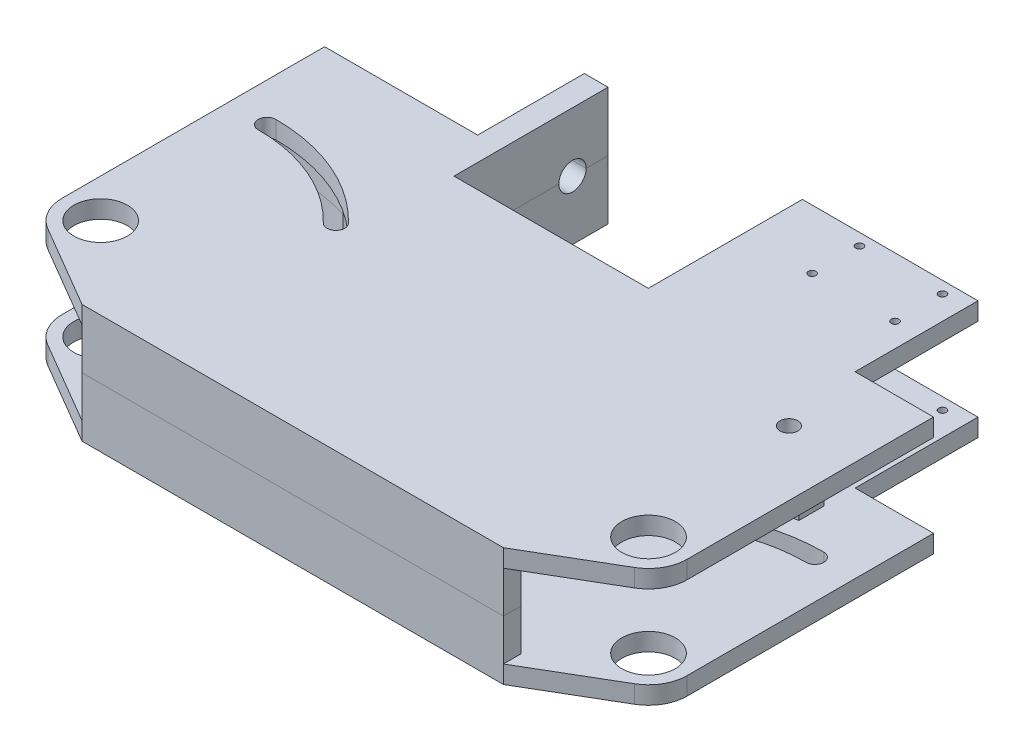
SolidWorks part; units mm, degrees
material "ABS"
ref_plane "Front Plane" through (0, 0, 0) normal (0, 0, 1) x (1, 0, 0)
ref_plane "Top Plane" through (0, 0, 0) normal (0, 1, 0) x (1, 0, 0)
ref_plane "Right Plane" through (0, 0, 0) normal (1, 0, 0) x (0, 0, -1)
sketch "Sketch1" plane through (0, 0, 0) normal (0, 1, 0) x (1, 0, 0)
  line L0 (0, 0) -> (0, 70.6916) construction
  line L1 (-112.9008, 0) -> (112.9008, 0)
  line L2 (166.7207, 38.2351) -> (89.7717, -234.2263) construction
  line L3 (126.8773, 49.4878) -> (49.9283, -222.9737) construction
  line L4 (146.799, 43.8615) -> (64.2237, -248.5217) construction
  line L5 (493.7687, -279.4) -> (979.2976, -279.4) construction
  line L6 (146.799, 43.8615) -> (146.799, 133.0155) construction
  line L7 (146.799, 133.0155) -> (-132.888, 133.0155) construction
  line L8 (19.05, -226.7236) -> (19.05, -291.7876) construction
  line L9 (-21.414, -217.1721) -> (256.1021, -295.5486) construction
  line L11 (146.799, 64.5625) -> (-146.799, 64.5625) construction
  line L12 (-146.799, 23.1605) -> (146.799, 23.1605) construction
  line L30 (-157.2662, 26.0018) -> (-112.9008, 0)
  line L31 (112.9008, 0) -> (157.2662, 26.0018)
  line L33 (-146.799, 43.8615) -> (-146.799, 133.0155) construction
  line L34 (-146.799, 133.0155) -> (132.888, 133.0155) construction
  line L38 (-167.5, 109.8697) -> (167.5, 109.8697) construction
  line L39 (-167.5, 43.8615) -> (-167.5, 184.5775)
  line L40 (-85.458, 241.7275) -> (-72.758, 241.7275)
  line L41 (-72.758, 241.7275) -> (-72.758, 159.1775)
  line L47 (125.4814, 175.878) -> (167.5, 175.878)
  line L51 (31.382, 159.1775) -> (31.382, 241.7275)
  line L52 (167.5, 43.8615) -> (167.5, 175.878)
  line L53 (31.382, 241.7275) -> (125.4814, 241.7275)
  line L54 (125.4814, 241.7275) -> (125.4814, 175.878)
  line L55 (68.3314, 209.9775) -> (112.7814, 235.3775) construction
  line L60 (112.7814, 235.3775) -> (68.3314, 235.3775) construction
  line L61 (112.7814, 235.3775) -> (112.7814, 209.9775) construction
  line L62 (112.7814, 209.9775) -> (68.3314, 209.9775) construction
  line L63 (68.3314, 235.3775) -> (68.3314, 209.9775) construction
  line L64 (112.7814, 209.9775) -> (68.3314, 235.3775) construction
  line L65 (-132.888, 184.5775) -> (-132.888, 81.4535) construction
  line L66 (-82.5723, 105.6948) -> (-146.799, 43.8615) construction
  line L67 (-85.458, 241.7275) -> (-85.458, 184.5775)
  line L68 (-85.458, 184.5775) -> (-167.5, 184.5775)
  line L69 (-72.758, 159.1775) -> (31.382, 159.1775)
  circle A0 centre (146.799, 43.8615) radius 14.351
  circle A2 centre (146.799, 43.8615) radius 20.701 construction
  circle A3 centre (69.85, -228.6) radius 14.351 construction
  circle A4 centre (69.85, -228.6) radius 20.701 construction
  circle A5 centre (69.85, -228.6) radius 50.8 construction
  circle A6 centre (99.1898, -124.7136) radius 50.8 construction
  circle A7 centre (-132.888, 133.0155) radius 4.7625
  circle A8 centre (-146.799, 43.8615) radius 14.351
  arc A9 (-157.2662, 26.0018) -> (-167.5, 43.8615) centre (-146.799, 43.8615) cw
  circle A10 centre (-132.888, 133.0155) radius 11.1125 construction
  circle A11 centre (146.799, 133.0155) radius 5.5563 construction
  circle A12 centre (-146.799, 43.8615) radius 20.701 construction
  arc A13 (-167.5, 43.8615) -> (-157.2662, 26.0018) centre (-146.799, 43.8615) cw construction
  circle A19 centre (132.888, 133.0155) radius 4.7625
  arc A20 (-146.799, 133.0155) -> (-82.5723, 105.6948) centre (-146.799, 43.8615) cw construction
  circle A28 centre (132.888, 133.0155) radius 11.1125 construction
  arc A35 (157.2662, 26.0018) -> (167.5, 43.8615) centre (146.799, 43.8615) ccw
  circle A39 centre (112.7814, 235.3775) radius 2.0193
  circle A40 centre (112.7814, 209.9775) radius 2.0193
  circle A41 centre (68.3314, 209.9775) radius 2.0193
  circle A42 centre (68.3314, 235.3775) radius 2.0193
  point P2 (85.3828, -173.6013)
  point P11 (0, 0)
  point P19 (19.05, -228.6)
  point P27 (83.6569, -179.7123)
  point P68 (-132.888, 133.0155)
  point P70 (90.5564, 222.6775)
  point P72 (0, 109.8697)
  point P78 (167.5, 109.8697)
  dimension "D2" = 28.702
  dimension "D6" = 101.6
  dimension "D12" = 9.525
  dimension "D16" = 11.1125
  dimension "D19" = 104.14
  dimension "D23" = 4.0386
  dimension "D5" = 89.154
  dimension "D7" = 6.35
  dimension "D8" = 279.4
  dimension "D9" = 279.687
  dimension "D10" = 296.926
  dimension "D11" = 19.05
  dimension "D13" = 146.799
  dimension "D17" = 6.35
  dimension "D18" = 94.742
  dimension "D20" = 82.55
  dimension "D21" = 57.15
  dimension "D25" = 6.35
  dimension "D22" = 25.4
  dimension "D24" = 44.45
  dimension "D26" = 12.7
  dimension "D27" = 36.9494
  dimension "D28" = 335
  dimension "D29" = 46.088
  dimension "D30" = 12.7
  dimension "D31" = 51.562
  dimension "D32" = 8.6995
  dimension "D3" = 6.35
  dimension "D4" = 6.35
  dimension "D14" = 6.35
  dimension "D15" = 6.35
extrude "Boss-Extrude1" add sketch "Sketch1" along normal mid plane 9.525 contours A0 A7 A8 region at (5.8545, 0, -103.4895)
sketch "Sketch6" plane through (0, 4.7625, 0) normal (0, 1, 0) x (1, 0, 0)
  line L11 (-112.9008, 9.525) -> (112.9008, 9.525)
  line L12 (-72.758, 159.1775) -> (125.4814, 159.1775)
  line L15 (-72.758, 241.7275) -> (-72.758, 159.1775) construction
  line L16 (-85.458, 241.7275) -> (-72.758, 241.7275) construction
  line L17 (-85.458, 241.7275) -> (-85.458, 184.5775) construction
  line L21 (-167.5, 43.8615) -> (-167.5, 184.5775) construction
  line L35 (-112.9008, 0) -> (112.9008, 0)
  line L38 (45.6521, 202.1035) -> (67.2858, 150.1296) construction
  line L39 (67.2858, 150.1296) -> (-83.7159, 144.9535) construction
  line L42 (115.9564, 136.6682) -> (115.9563, 202.1035) construction
  line L43 (115.9563, 202.1035) -> (45.6521, 202.1035) construction
  line L47 (31.3702, 211.6285) -> (53.2025, 159.1775) construction
  line L48 (125.4814, 145.7962) -> (125.4813, 211.6285) construction
  line L49 (125.4813, 211.6285) -> (31.3702, 211.6285) construction
  line L50 (125.4814, 241.7275) -> (125.4814, 175.878) construction
  line L51 (125.4814, 159.1775) -> (125.4814, 145.7962)
  line L53 (116.5914, 143.5241) -> (-116.5914, 143.5241)
  line L55 (-154.5631, 33.9416) -> (-112.9008, 9.525) construction
  line L56 (-83.7041, 194.8963) -> (-159.2482, 41.937) construction
  line L58 (112.9008, 9.525) -> (158.0561, 35.8748) construction
  line L59 (160.5644, 42.8499) -> (160.96, 134.7521) construction
  line L61 (160.96, 134.7521) -> (115.9564, 136.6682) construction
  line L63 (112.9008, 0) -> (112.9008, 9.525)
  line L64 (-83.7159, 144.9535) -> (-83.7041, 194.8963) construction
  line L65 (-83.7041, 194.8963) -> (-83.7041, 194.8963) construction
  line L66 (146.799, 43.8615) -> (146.799, 133.0155) construction
  line L67 (-85.458, 184.5775) -> (-167.5, 184.5775) construction
  line L68 (146.799, 43.8615) -> (146.799, 133.0155) construction
  line L69 (-146.799, 43.8615) -> (-146.799, 133.0155) construction
  line L70 (0, 0) -> (0, 175.4088) construction
  line L72 (-72.758, 241.7275) -> (-72.758, 159.1775)
  line L73 (-85.458, 241.7275) -> (-72.758, 241.7275)
  line L74 (-112.9008, 9.525) -> (-112.9008, 0)
  line L75 (-86.8791, 209.9775) -> (-168.9211, 43.8615) construction
  line L76 (-159.8532, 26.0016) -> (-115.4863, 0) construction
  line L78 (170.5244, 143.8785) -> (125.4814, 145.7962) construction
  line L79 (170.0881, 42.5228) -> (170.5244, 143.8785) construction
  line L80 (115.4767, 0) -> (164.3938, 28.545) construction
  line L81 (-115.4863, 0) -> (115.4767, 0) construction
  line L82 (-85.458, 241.7275) -> (-85.458, 184.5775)
  line L83 (-167.5, 145.9233) -> (-167.5, 184.5775)
  line L84 (-85.458, 184.5775) -> (-167.5, 184.5775)
  line L85 (-112.9008, 0) -> (112.9008, 0) construction
  line L97 (-74.1755, 209.9775) -> (-86.8791, 209.9775) construction
  line L98 (-74.1886, 154.8106) -> (-74.1755, 209.9775) construction
  line L99 (53.2025, 159.1775) -> (-74.1886, 154.8106) construction
  circle A0 centre (-146.799, 133.0155) radius 12.7 construction
  circle A1 centre (146.799, 133.0155) radius 5.5563 construction
  circle A6 centre (-132.888, 133.0155) radius 4.7625 construction
  circle A7 centre (146.799, 133.0155) radius 5.5563 construction
  circle A10 centre (-132.888, 133.0155) radius 4.7625
  arc A16 (125.4814, 145.7962) -> (116.5914, 143.5241) centre (146.799, 43.8615) ccw
  arc A19 (-159.2482, 41.937) -> (-154.5631, 33.9416) centre (-146.799, 43.8615) ccw construction
  circle A20 centre (132.888, 133.0155) radius 4.7625 construction
  arc A21 (158.0561, 35.8748) -> (160.5644, 42.8499) centre (146.799, 43.8615) ccw construction
  circle A23 centre (132.888, 133.0155) radius 4.7625
  circle A27 centre (-146.799, 133.0155) radius 5.5563 construction
  circle A28 centre (146.799, 133.0155) radius 11.9063 construction
  arc A33 (-116.5914, 143.5241) -> (-167.5, 145.9233) centre (-146.799, 43.8615) ccw
  arc A35 (-168.9211, 43.8615) -> (-159.8532, 26.0016) centre (-146.799, 43.8615) ccw construction
  circle A36 centre (-146.799, 43.8615) radius 14.351 construction
  arc A37 (164.3938, 28.545) -> (170.0881, 42.5228) centre (146.799, 43.8615) ccw construction
  dimension "D3" = 25.4
  dimension "D5" = 104.14
  dimension "D6" = 104.14
  dimension "D1" = 8.89
  dimension "D2" = 9.525
  dimension "D7" = 6.35
extrude "Boss-Extrude3" add sketch "Sketch6" along normal blind 22.225 contours A33 L83 L84 L82 L73 L72 L12 L51 A16 L53 | L35 L63 L11 L74
sketch "Sketch5" plane through (0, 0, 0) normal (1, 0, 0) x (0, 0, -1)
  line L0 (215.3451, 26.9875) -> (230.0098, 26.9875)
  line L1 (219.0113, 20.6375) -> (226.3436, 20.6375) construction
  line L2 (226.3436, 20.6375) -> (230.0098, 26.9875) construction
  line L3 (230.0098, 26.9875) -> (226.3436, 33.3375) construction
  line L4 (159.1775, -4.7625) -> (241.7275, -4.7625)
  line L5 (241.7275, -4.7625) -> (241.7275, 26.9875)
  line L6 (241.7275, 26.9875) -> (159.1775, 26.9875)
  line L7 (159.1775, 26.9875) -> (159.1775, -4.7625)
  line L8 (159.1775, -4.7625) -> (241.7275, -4.7625) construction
  line L9 (241.7275, -4.7625) -> (241.7275, 26.9875) construction
  line L11 (159.1775, 26.9875) -> (159.1775, -4.7625) construction
  line L12 (226.3436, 33.3375) -> (219.0113, 33.3375) construction
  line L13 (219.0113, 33.3375) -> (215.3451, 26.9875) construction
  line L14 (215.3451, 26.9875) -> (219.0113, 20.6375) construction
  line L19 (241.7275, 26.9875) -> (159.1775, 26.9875)
  arc A0 (215.3451, 26.9875) -> (230.0098, 26.9875) centre (222.6775, 26.9875) ccw
  circle A1 centre (222.6775, 26.9875) radius 6.35 construction
  point P5 (0, 0)
  point P6 (200.9436, 35.0888)
  dimension "D2" = 63.5
  dimension "D3" = 12.7
  dimension "D1" = 0
extrude "Cut-Extrude1" cut sketch "Sketch5" against normal up to surface (167.5 mm away) contours L0 A0 region at (0, 23.8756, -222.6775) up to face at (-167.5, 8.9958, -124.7874)
mirror "Mirror3" about plane through (-146.799, 26.9875, -43.8615) normal (0, 1, 0) of bodies 107
sketch "Sketch7" plane through (0, 26.9875, 0) normal (0, 1, 0) x (1, 0, 0)
  line L0 (-146.799, 43.8615) -> (-146.799, 133.0155) construction
  line L1 (-82.5723, 105.6948) -> (-146.799, 43.8615) construction
  line L2 (-146.799, 43.8615) -> (-146.799, 133.0155) construction
  line L3 (-82.5723, 105.6948) -> (-146.799, 43.8615) construction
  line L7 (0, 0) -> (0, 235.7912) construction
  arc A0 (-82.5723, 105.6948) -> (-146.799, 133.0155) centre (-146.799, 43.8615) ccw construction
  arc A1 (-82.5723, 105.6948) -> (-146.799, 133.0155) centre (-146.799, 43.8615) ccw construction
  arc A2 (-146.799, 133.0155) -> (-82.5723, 105.6948) centre (-146.799, 43.8615) cw construction
  arc A3 (-79.1413, 108.9979) -> (-146.799, 137.778) centre (-146.799, 43.8615) ccw
  arc A4 (-86.0032, 102.3917) -> (-146.799, 128.253) centre (-146.799, 43.8615) ccw
  arc A5 (-86.0032, 102.3917) -> (-79.1413, 108.9979) centre (-82.5723, 105.6948) ccw
  arc A6 (-146.799, 137.778) -> (-146.799, 128.253) centre (-146.799, 133.0155) ccw
  arc A7 (146.799, 133.0155) -> (82.5723, 105.6948) centre (146.799, 43.8615) ccw construction
  arc A8 (79.1413, 108.9979) -> (146.799, 137.778) centre (146.799, 43.8615) cw
  arc A9 (86.0032, 102.3917) -> (146.799, 128.253) centre (146.799, 43.8615) cw
  arc A10 (86.0032, 102.3917) -> (79.1413, 108.9979) centre (82.5723, 105.6948) cw
  arc A11 (146.799, 137.778) -> (146.799, 128.253) centre (146.799, 133.0155) cw
  point P5 (-111.901, 125.9015)
  point P15 (111.901, 125.9015)
  dimension "D1" = 4.7625
extrude "Cut-Extrude3" cut sketch "Sketch7" against normal through all contours A8 A11 A9 A10
extrude "Cut-Extrude8" cut sketch "Sketch7<5>" along normal through all contours A3 A6 A4 A5
sketch "Sketch7<5>" plane through (0, 26.9875, 0) normal (0, 1, 0) x (1, 0, 0) same geometry as "Sketch7"
sketch "Sketch8" plane through (0, -4.7625, 0) normal (0, -1, 0) x (1, 0, 0)
  arc A0 (129.2856, -136.1306) -> (135.3702, -137.08) centre (132.888, -133.0155) ccw construction
  arc A1 (129.2856, -136.1306) -> (135.3702, -137.08) centre (132.888, -133.0155) ccw
  arc A2 (129.2856, -136.1306) -> (135.3702, -137.08) centre (146.799, -43.8615) ccw
  arc M6 (135.3702, -137.08) -> (129.2856, -136.1306) centre (132.888, -133.0155) cw
extrude "Boss-Extrude4" add sketch "Sketch8" against normal up to surface (9.525 mm away) contours A2 M6 region at (132.2544, -4.7625, -137.0761) up to face at (68.3314, 4.7625, -233.3582)
sketch "Sketch9" plane through (0, 58.7375, 0) normal (0, 1, 0) x (1, 0, 0)
  arc A0 (-129.2856, 136.1306) -> (-135.3702, 137.08) centre (-132.888, 133.0155) ccw construction
  arc A1 (-129.2856, 136.1306) -> (-135.3702, 137.08) centre (-132.888, 133.0155) ccw
  arc A2 (-135.3702, 137.08) -> (-129.2856, 136.1306) centre (-146.799, 43.8615) cw
  arc M6 (-135.3702, 137.08) -> (-129.2856, 136.1306) centre (-132.888, 133.0155) cw
extrude "Boss-Extrude5" add sketch "Sketch9" against normal up to surface (9.525 mm away) contours A2 M6 region at (-132.2544, 58.7375, -137.0761) up to face at (68.3314, 49.2125, -233.3582)
equation "\"gripwidth\"= 9in"
equation "\"bearinghole\"= 1.125"
equation "\"wheeldia\"= 4"
equation "\"firstlength\"= 3.2"
equation "\"secondlength\"= \"firstlength\" * 10 / 3"
equation "\"overallpistonlength\"= 9.51"
equation "\"secondlengthprime\"= 11.6875"
equation "\"firstlengthprime\"= \"secondlengthprime\" * 3 / 10"
